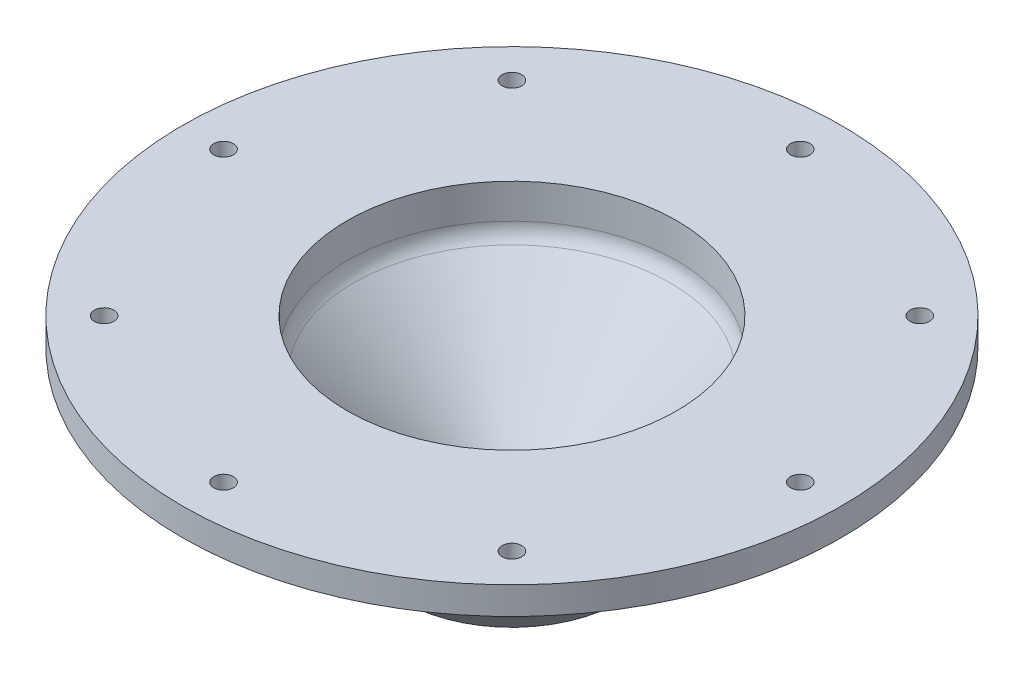
SolidWorks part; units mm, degrees
material "7075-T6 (SN)"
ref_plane "Front Plane" through (0, 0, 0) normal (0, 0, 1) x (1, 0, 0)
ref_plane "Top Plane" through (0, 0, 0) normal (0, 1, 0) x (1, 0, 0)
ref_plane "Right Plane" through (0, 0, 0) normal (1, 0, 0) x (0, 0, -1)
sketch "Sketch1" plane through (0, 0, 0) normal (0, 1, 0) x (1, 0, 0)
  circle A0 centre (0, 0) radius 38.1
  dimension "D1" = 76.2
extrude "Boss-Extrude1" add sketch "Sketch1" along normal blind 3.175
hole_wizard "Tap Drill for #4-40 Tap1" positions "Sketch3" profile "Sketch4" hole size "#4-40" standard "ANSI Inch" end condition through all
sketch "Sketch3" plane through (0, 0, 0) normal (0, -1, 0) x (-1, 0, 0)
  point P0 (0, -33.3375)
  dimension "D1" = 33.3375
sketch "Sketch4" plane through (0, 0, 33.3375) normal (1, 0, 0) x (0, 0, -1)
  line L0 (0, 0) -> (0, 3.175)
  line L1 (0, 3.175) -> (1.1303, 3.175)
  line L2 (1.1303, 3.175) -> (1.1303, 0)
  line L5 (1.1303, 0) -> (0, 0)
  line L11 (0, -6.35) -> (0, 107.95) construction
  dimension "Thru Hole Dia." = 2.2606
  dimension "Thru Hole Depth" = 3.175
pattern_circular "CirPattern1" count 8 over 360 about axis through (0, 0, 0) along (0, 1, 0) of "Tap Drill for #4-40 Tap1"
sketch "Sketch5" plane through (0, 0, 0) normal (0, -1, 0) x (1, 0, 0)
  circle A0 centre (0, 0) radius 25.4
  dimension "D1" = 50.8
extrude "Boss-Extrude2" add sketch "Sketch5" along normal blind 19.05
sketch "Sketch6" plane through (0, -19.05, 0) normal (0, -1, 0) x (1, 0, 0)
  circle A0 centre (0, 0) radius 4.7625
  dimension "D1" = 9.525
extrude "Cut-Extrude1" cut sketch "Sketch6" against normal through all both and the other way through all
sketch "Sketch7" plane through (0, 3.175, 0) normal (0, 1, 0) x (1, 0, 0)
  circle A0 centre (0, 0) radius 19.05
  dimension "D1" = 38.1
extrude "Cut-Extrude2" cut sketch "Sketch7" against normal blind 5.08
sketch "Sketch8" plane through (0, -1.905, 0) normal (0, 1, 0) x (1, 0, 0)
  circle A0 centre (0, 0) radius 19.05
  circle A1 centre (0, 0) radius 19.05 construction
  dimension "D1" = 0
ref_plane "Plane1" through (0, -15.875, 0) normal (0, -1, 0) x (-1, 0, 0)
sketch "Sketch9" plane through (0, -15.875, 0) normal (0, -1, 0) x (-1, 0, 0)
  circle A0 centre (0, 0) radius 4.7625
  circle A1 centre (0, 0) radius 4.7625 construction
  dimension "D1" = 0
loft "Cut-Loft1" cut profiles "Sketch8", "Sketch9" connector at (0, -1.905, 19.05) connector at (-1.301, -15.875, 4.5814)
chamfer "Chamfer1" distance 12.7 angle 45 1 edges at (0, -19.05, -25.4)
fillet "Fillet1" radius 2.54 1 edges at (0, 0, 25.4)
fillet "Fillet2" radius 2.54 1 edges at (0, -1.905, 19.05)
